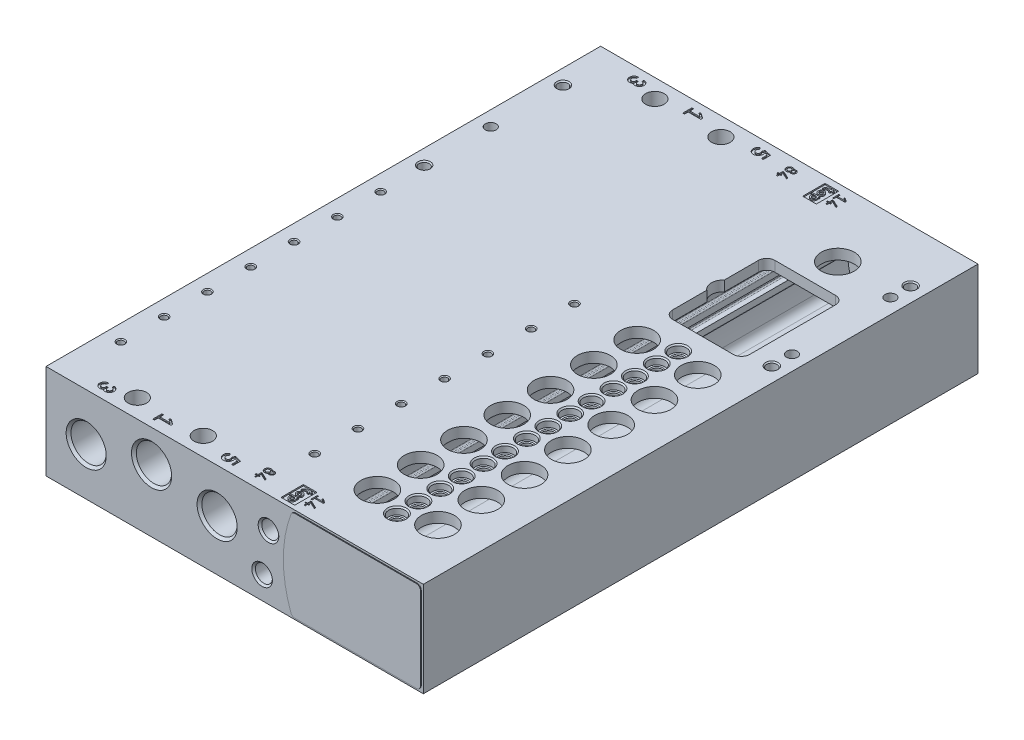
SolidWorks part; units mm, degrees
ref_plane "Ebene vorne" through (0, 0, 0) normal (0, 0, 1) x (1, 0, 0)
ref_plane "Ebene oben" through (0, 0, 0) normal (0, 1, 0) x (1, 0, 0)
ref_plane "Ebene rechts" through (0, 0, 0) normal (1, 0, 0) x (0, 0, -1)
sketch "Skizze1" plane through (0, 0, 0) normal (0, 0, 1) x (1, 0, 0)
  line L0 (0, -23) -> (91.5, -23)
  line L1 (91.5, -23) -> (91.5, 0)
  line L2 (91.5, 0) -> (0, 0)
  line L3 (0, 0) -> (0, -23)
  line L4 (59.6, -8.95) -> (59.6, -10.45)
  line L5 (59.9, -10.75) -> (61.1, -10.75)
  line L6 (61.1, -10.75) -> (61.1, -12.2)
  line L7 (60.8, -12.5) -> (60.0805, -12.5)
  line L8 (62.3938, -19.25) -> (83.8, -19.25)
  line L9 (85.8, -17.25) -> (85.8, -10.75)
  line L10 (85.8, -10.75) -> (87, -10.75)
  line L11 (87.3, -10.45) -> (87.3, -8.95)
  line L12 (87, -8.65) -> (85.8, -8.65)
  line L13 (85.8, -8.65) -> (85.8, -4.5)
  line L14 (83.8, -2.5) -> (62.71, -2.5)
  line L15 (60.4868, -6.9) -> (60.8, -6.9)
  line L16 (61.1, -7.2) -> (61.1, -8.65)
  line L17 (61.1, -8.65) -> (59.9, -8.65)
  arc A0 (59.6, -10.45) -> (59.9, -10.75) centre (59.9, -10.45) ccw
  arc A1 (61.1, -12.2) -> (60.8, -12.5) centre (60.8, -12.2) cw
  arc A2 (60.0805, -12.5) -> (59.7809, -12.8141) centre (60.0805, -12.8) ccw
  arc A3 (59.7809, -12.8141) -> (60.4433, -17.6923) centre (87.75, -11.5) ccw
  arc A4 (60.4433, -17.6923) -> (62.3938, -19.25) centre (62.3938, -17.25) ccw
  arc A5 (83.8, -19.25) -> (85.8, -17.25) centre (83.8, -17.25) ccw
  arc A6 (87, -10.75) -> (87.3, -10.45) centre (87, -10.45) ccw
  arc A7 (87.3, -8.95) -> (87, -8.65) centre (87, -8.95) ccw
  arc A8 (85.8, -4.5) -> (83.8, -2.5) centre (83.8, -4.5) ccw
  arc A9 (62.71, -2.5) -> (60.7839, -3.9615) centre (62.71, -4.5) ccw
  arc A10 (60.7839, -3.9615) -> (60.1916, -6.5469) centre (87.75, -11.5) ccw
  arc A11 (60.1916, -6.5469) -> (60.4868, -6.9) centre (60.4868, -6.6) ccw
  arc A12 (60.8, -6.9) -> (61.1, -7.2) centre (60.8, -7.2) cw
  arc A13 (59.9, -8.65) -> (59.6, -8.95) centre (59.9, -8.95) ccw
extrude "Aufsatz-Linear austragen1" add sketch "Skizze1" along normal blind 134.5
ref_plane "Ebene1" through (9.75, 0, 0) normal (1, 0, 0) x (0, 0, -1)
sketch "Skizze2" plane through (9.75, 0, 0) normal (1, 0, 0) x (0, 0, -1)
  line L0 (0, -11.5) -> (0, -16.364)
  line L1 (0, -16.364) -> (-0.581, -15.783)
  line L2 (-0.581, -15.783) -> (-9.5, -15.783)
  line L3 (-9.5, -15.783) -> (-9.5, -11.5)
  line L4 (-9.5, -11.5) -> (0, -11.5)
  line L5 (-9.5, -11.5) -> (0, -11.5) construction
revolve "Schnitt-Rotation1" cut sketch "Skizze2" angle 360 about L5 reverse direction yes
cosmetic thread "Gewindedarstellung1" parameters "D1"=7, "D2"=9.728
sketch "Skizze3" plane through (9.75, 0, 0) normal (1, 0, 0) x (0, 0, -1)
  line L0 (-125, -11.5) -> (-125, -15.783)
  line L1 (-125, -15.783) -> (-133.919, -15.783)
  line L2 (-133.919, -15.783) -> (-134.5, -16.364)
  line L3 (-134.5, -16.364) -> (-134.5, -11.5)
  line L4 (-134.5, -11.5) -> (-125, -11.5)
  line L5 (-134.5, -11.5) -> (-125, -11.5) construction
revolve "Schnitt-Rotation2" cut sketch "Skizze3" angle 360 about L5 reverse direction yes
cosmetic thread "Gewindedarstellung2" parameters "D1"=7, "D2"=9.728
ref_plane "Ebene2" through (25.6, 0, 0) normal (1, 0, 0) x (0, 0, -1)
sketch "Skizze4" plane through (25.6, 0, 0) normal (1, 0, 0) x (0, 0, -1)
  line L0 (0, -7.8) -> (0, -12.664)
  line L1 (0, -12.664) -> (-0.581, -12.083)
  line L2 (-0.581, -12.083) -> (-9.5, -12.083)
  line L3 (-9.5, -12.083) -> (-9.5, -7.8)
  line L4 (-9.5, -7.8) -> (0, -7.8)
  line L5 (-9.5, -7.8) -> (0, -7.8) construction
revolve "Schnitt-Rotation3" cut sketch "Skizze4" angle 360 about L5 reverse direction yes
cosmetic thread "Gewindedarstellung3" parameters "D1"=7, "D2"=9.728
sketch "Skizze5" plane through (25.6, 0, 0) normal (1, 0, 0) x (0, 0, -1)
  line L0 (-125, -7.8) -> (-125, -12.083)
  line L1 (-125, -12.083) -> (-133.919, -12.083)
  line L2 (-133.919, -12.083) -> (-134.5, -12.664)
  line L3 (-134.5, -12.664) -> (-134.5, -7.8)
  line L4 (-134.5, -7.8) -> (-125, -7.8)
  line L5 (-134.5, -7.8) -> (-125, -7.8) construction
revolve "Schnitt-Rotation4" cut sketch "Skizze5" angle 360 about L5 reverse direction yes
cosmetic thread "Gewindedarstellung4" parameters "D1"=7, "D2"=9.728
ref_plane "Ebene3" through (41.5, 0, 0) normal (1, 0, 0) x (0, 0, -1)
sketch "Skizze6" plane through (41.5, 0, 0) normal (1, 0, 0) x (0, 0, -1)
  line L0 (0, -10.6) -> (0, -15.464)
  line L1 (0, -15.464) -> (-0.581, -14.883)
  line L2 (-0.581, -14.883) -> (-9.5, -14.883)
  line L3 (-9.5, -14.883) -> (-9.5, -10.6)
  line L4 (-9.5, -10.6) -> (0, -10.6)
  line L5 (-9.5, -10.6) -> (0, -10.6) construction
revolve "Schnitt-Rotation5" cut sketch "Skizze6" angle 360 about L5 reverse direction yes
cosmetic thread "Gewindedarstellung5" parameters "D1"=7, "D2"=9.728
sketch "Skizze7" plane through (41.5, 0, 0) normal (1, 0, 0) x (0, 0, -1)
  line L0 (-125, -10.6) -> (-125, -14.883)
  line L1 (-125, -14.883) -> (-133.919, -14.883)
  line L2 (-133.919, -14.883) -> (-134.5, -15.464)
  line L3 (-134.5, -15.464) -> (-134.5, -10.6)
  line L4 (-134.5, -10.6) -> (-125, -10.6)
  line L5 (-134.5, -10.6) -> (-125, -10.6) construction
revolve "Schnitt-Rotation6" cut sketch "Skizze7" angle 360 about L5 reverse direction yes
cosmetic thread "Gewindedarstellung6" parameters "D1"=7, "D2"=9.728
ref_plane "Ebene4" through (52.4, 0, 0) normal (1, 0, 0) x (0, 0, -1)
sketch "Skizze8" plane through (52.4, 0, 0) normal (1, 0, 0) x (0, 0, -1)
  line L0 (0, -17.5) -> (0, -20)
  line L1 (0, -20) -> (-0.433, -19.567)
  line L2 (-0.433, -19.567) -> (-5, -19.567)
  line L3 (-5, -19.567) -> (-5, -17.5)
  line L4 (-5, -17.5) -> (0, -17.5)
  line L5 (-5, -17.5) -> (0, -17.5) construction
revolve "Schnitt-Rotation7" cut sketch "Skizze8" angle 360 about L5 reverse direction yes
cosmetic thread "Gewindedarstellung7" parameters "D1"=5, "D2"=5
sketch "Skizze9" plane through (52.4, 0, 0) normal (1, 0, 0) x (0, 0, -1)
  line L0 (-129.5, -17.5) -> (-129.5, -19.567)
  line L1 (-129.5, -19.567) -> (-134.067, -19.567)
  line L2 (-134.067, -19.567) -> (-134.5, -20)
  line L3 (-134.5, -20) -> (-134.5, -17.5)
  line L4 (-134.5, -17.5) -> (-129.5, -17.5)
  line L5 (-134.5, -17.5) -> (-129.5, -17.5) construction
revolve "Schnitt-Rotation8" cut sketch "Skizze9" angle 360 about L5 reverse direction yes
cosmetic thread "Gewindedarstellung8" parameters "D1"=5, "D2"=5
ref_plane "Ebene5" through (53.95, 0, 0) normal (1, 0, 0) x (0, 0, -1)
sketch "Skizze10" plane through (53.95, 0, 0) normal (1, 0, 0) x (0, 0, -1)
  line L0 (0, -7.5) -> (0, -10)
  line L1 (0, -10) -> (-0.433, -9.567)
  line L2 (-0.433, -9.567) -> (-5, -9.567)
  line L3 (-5, -9.567) -> (-5, -7.5)
  line L4 (-5, -7.5) -> (0, -7.5)
  line L5 (-5, -7.5) -> (0, -7.5) construction
revolve "Schnitt-Rotation9" cut sketch "Skizze10" angle 360 about L5 reverse direction yes
cosmetic thread "Gewindedarstellung9" parameters "D1"=5, "D2"=5
sketch "Skizze11" plane through (53.95, 0, 0) normal (1, 0, 0) x (0, 0, -1)
  line L0 (-129.5, -7.5) -> (-129.5, -9.567)
  line L1 (-129.5, -9.567) -> (-134.067, -9.567)
  line L2 (-134.067, -9.567) -> (-134.5, -10)
  line L3 (-134.5, -10) -> (-134.5, -7.5)
  line L4 (-134.5, -7.5) -> (-129.5, -7.5)
  line L5 (-134.5, -7.5) -> (-129.5, -7.5) construction
revolve "Schnitt-Rotation10" cut sketch "Skizze11" angle 360 about L5 reverse direction yes
cosmetic thread "Gewindedarstellung10" parameters "D1"=5, "D2"=5
hole_wizard "Bohrung1" positions "Skizze13" profile "Skizze12" legacy
sketch "Skizze13" plane through (0, 0, 0) normal (0, 1, 0) x (1, 0, 0)
  point P0 (17.65, -4.5)
sketch "Skizze12" plane through (17.65, 0, 4.5) normal (1, 0, 0) x (0, 0, 1)
  line L0 (0, 0) -> (0, 23)
  line L1 (0, 23) -> (2.25, 23)
  line L2 (2.25, 23) -> (2.25, 0)
  line L3 (2.25, 0) -> (0, 0)
  line L4 (0, 110) -> (0, -10) construction
  dimension "Durchmesser" = 4.5
  dimension "Tiefe" = 23
sketch "Skizze14" plane through (0, 0, 0) normal (0, 1, 0) x (1, 0, 0)
  line L0 (17.65, -4.5) -> (33.65, -4.5)
  line L1 (17.65, -4.5) -> (17.65, -130)
pattern_linear "Lineares Muster1" count 2 spacing 16 along (1, 0, 0) count 2 spacing 125.5 along (0, 0, 1) of "Bohrung1"
hole_wizard "Bohrung2" positions "Skizze16" profile "Skizze15" legacy
sketch "Skizze16" plane through (0, 0, 0) normal (0, 1, 0) x (1, 0, 0)
  point P0 (80.8, -57.25)
sketch "Skizze15" plane through (80.8, 0, 57.25) normal (1, 0, 0) x (0, 0, 1)
  line L0 (0, 0) -> (0, 5)
  line L1 (0, 5) -> (4, 5)
  line L2 (4, 5) -> (4, 0)
  line L3 (4, 0) -> (0, 0)
  line L4 (0, 110) -> (0, -10) construction
  dimension "Durchmesser" = 8
  dimension "Tiefe" = 5
sketch "Skizze17" plane through (0, 0, 0) normal (0, 1, 0) x (1, 0, 0)
  line L0 (80.8, -57.25) -> (80.8, -120.25)
pattern_linear "Lineares Muster2" count 7 spacing 10.5 along (0, 0, 1) of "Bohrung2"
hole_wizard "Bohrung3" positions "Skizze19" profile "Skizze18" legacy
sketch "Skizze19" plane through (0, 0, 0) normal (0, 1, 0) x (1, 0, 0)
  point P0 (66.1, -57.25)
sketch "Skizze18" plane through (66.1, 0, 57.25) normal (1, 0, 0) x (0, 0, 1)
  line L0 (0, 0) -> (0, 5)
  line L1 (0, 5) -> (4, 5)
  line L2 (4, 5) -> (4, 0)
  line L3 (4, 0) -> (0, 0)
  line L4 (0, 110) -> (0, -10) construction
  dimension "Durchmesser" = 8
  dimension "Tiefe" = 5
sketch "Skizze20" plane through (0, 0, 0) normal (0, 1, 0) x (1, 0, 0)
  line L0 (66.1, -57.25) -> (66.1, -120.25)
pattern_linear "Lineares Muster3" count 7 spacing 10.5 along (0, 0, 1) of "Bohrung3"
ref_plane "Ebene6" through (73.45, 0, 0) normal (1, 0, 0) x (0, 0, -1)
sketch "Skizze21" plane through (73.45, 0, 0) normal (1, 0, 0) x (0, 0, -1)
  line L0 (-54.65, -3) -> (-56, -3)
  line L1 (-56, -3) -> (-56, -1.9)
  line L2 (-56, -1.9) -> (-56.2, -1.7)
  line L3 (-56.2, -1.7) -> (-56.65, -1.7)
  line L4 (-56.65, -1.7) -> (-56.65, -0.3)
  line L5 (-56.65, -0.3) -> (-56.95, 0)
  line L6 (-56.95, 0) -> (-54.65, 0)
  line L7 (-54.65, 0) -> (-54.65, -3)
  line L8 (-54.65, 0) -> (-54.65, -3) construction
revolve "Schnitt-Rotation11" cut sketch "Skizze21" angle 360 about L8 reverse direction yes
sketch "Skizze22" plane through (0, 0, 0) normal (0, 1, 0) x (1, 0, 0)
  line L0 (73.45, -54.65) -> (73.45, -117.65)
pattern_linear "Lineares Muster4" count 7 spacing 10.5 along (0, 0, 1) of "Schnitt-Rotation11"
sketch "Skizze23" plane through (73.45, 0, 0) normal (1, 0, 0) x (0, 0, -1)
  line L0 (-59.85, -3) -> (-61.2, -3)
  line L1 (-61.2, -3) -> (-61.2, -1.9)
  line L2 (-61.2, -1.9) -> (-61.4, -1.7)
  line L3 (-61.4, -1.7) -> (-61.85, -1.7)
  line L4 (-61.85, -1.7) -> (-61.85, -0.3)
  line L5 (-61.85, -0.3) -> (-62.15, 0)
  line L6 (-62.15, 0) -> (-59.85, 0)
  line L7 (-59.85, 0) -> (-59.85, -3)
  line L8 (-59.85, 0) -> (-59.85, -3) construction
revolve "Schnitt-Rotation12" cut sketch "Skizze23" angle 360 about L8 reverse direction yes
sketch "Skizze24" plane through (0, 0, 0) normal (0, 1, 0) x (1, 0, 0)
  line L0 (73.45, -59.85) -> (73.45, -122.85)
pattern_linear "Lineares Muster5" count 7 spacing 10.5 along (0, 0, 1) of "Schnitt-Rotation12"
ref_plane "Ebene7" through (50.9, 0, 0) normal (1, 0, 0) x (0, 0, -1)
hole_wizard "Bohrung4" positions "Skizze26" profile "Skizze25" legacy
sketch "Skizze26" plane through (0, 0, 0) normal (0, 1, 0) x (1, 0, 0)
  point P0 (50.9, -57.25)
sketch "Skizze25" plane through (50.9, 0, 57.25) normal (1, 0, 0) x (0, 0, 1)
  line L0 (0, 0) -> (0, 5.7524)
  line L1 (0, 5.7524) -> (0.7835, 5.3)
  line L2 (0.7835, 5.3) -> (0.7835, 0.2165)
  line L3 (0.7835, 0.2165) -> (1, 0)
  line L4 (1, 0) -> (0, 0)
  line L5 (0, -14.3089) -> (0, 102.4216) construction
  line L6 (0, 5.7524) -> (-0.7835, 5.3) construction
  line L7 (-0.7835, 0.2165) -> (-1, 0) construction
  dimension "Durchmesser" = 1.567
  dimension "Tiefe" = 5.3
  dimension "Senkdurchmesser1" = 2
  dimension "Senkwinkel1" = 90
  dimension "Spitzenwinkel" = 120
cosmetic thread "Gewindedarstellung11" parameters "D1"=4, "D2"=2
sketch "Skizze27" plane through (0, 0, 0) normal (0, 1, 0) x (1, 0, 0)
  line L0 (50.9, -57.25) -> (50.9, -120.25)
pattern_linear "Lineares Muster6" count 7 spacing 10.5 along (0, 0, 1) of "Bohrung4"
ref_plane "Ebene8" through (3.9, 0, 0) normal (1, 0, 0) x (0, 0, -1)
hole_wizard "Bohrung5" positions "Skizze29" profile "Skizze28" legacy
sketch "Skizze29" plane through (0, 0, 0) normal (0, 1, 0) x (1, 0, 0)
  point P0 (3.9, -57.25)
sketch "Skizze28" plane through (3.9, 0, 57.25) normal (1, 0, 0) x (0, 0, 1)
  line L0 (0, 0) -> (0, 5.7524)
  line L1 (0, 5.7524) -> (0.7835, 5.3)
  line L2 (0.7835, 5.3) -> (0.7835, 0.2165)
  line L3 (0.7835, 0.2165) -> (1, 0)
  line L4 (1, 0) -> (0, 0)
  line L5 (0, -14.3089) -> (0, 102.4216) construction
  line L6 (0, 5.7524) -> (-0.7835, 5.3) construction
  line L7 (-0.7835, 0.2165) -> (-1, 0) construction
  dimension "Durchmesser" = 1.567
  dimension "Tiefe" = 5.3
  dimension "Senkdurchmesser1" = 2
  dimension "Senkwinkel1" = 90
  dimension "Spitzenwinkel" = 120
cosmetic thread "Gewindedarstellung12" parameters "D1"=4, "D2"=2
sketch "Skizze30" plane through (0, 0, 0) normal (0, 1, 0) x (1, 0, 0)
  line L0 (3.9, -57.25) -> (3.9, -120.25)
pattern_linear "Lineares Muster7" count 7 spacing 10.5 along (0, 0, 1) of "Bohrung5"
hole_wizard "Bohrung6" positions "Skizze32" profile "Skizze31" legacy
sketch "Skizze32" plane through (0, 0, 0) normal (0, 1, 0) x (1, 0, 0)
  point P0 (74, -16.5)
sketch "Skizze31" plane through (74, 0, 16.5) normal (1, 0, 0) x (0, 0, 1)
  line L0 (0, 0) -> (0, 2.5)
  line L1 (0, 2.5) -> (4, 2.5)
  line L2 (4, 2.5) -> (4, 0)
  line L3 (4, 0) -> (0, 0)
  line L4 (0, 110) -> (0, -10) construction
  dimension "Durchmesser" = 8
  dimension "Tiefe" = 2.5
ref_plane "Ebene9" through (3.6, 0, 0) normal (1, 0, 0) x (0, 0, -1)
hole_wizard "Bohrung7" positions "Skizze34" profile "Skizze33" legacy
sketch "Skizze34" plane through (0, 0, 0) normal (0, 1, 0) x (1, 0, 0)
  point P0 (3.6, -12.75)
sketch "Skizze33" plane through (3.6, 0, 12.75) normal (1, 0, 0) x (0, 0, 1)
  line L0 (0, 0) -> (0, 7.7099)
  line L1 (0, 7.7099) -> (1.2295, 7)
  line L2 (1.2295, 7) -> (1.2295, 0.2705)
  line L3 (1.2295, 0.2705) -> (1.5, 0)
  line L4 (1.5, 0) -> (0, 0)
  line L5 (0, -14.3089) -> (0, 102.4216) construction
  line L6 (0, 7.7099) -> (-1.2295, 7) construction
  line L7 (-1.2295, 0.2705) -> (-1.5, 0) construction
  dimension "Durchmesser" = 2.459
  dimension "Tiefe" = 7
  dimension "Senkdurchmesser1" = 3
  dimension "Senkwinkel1" = 90
  dimension "Spitzenwinkel" = 120
cosmetic thread "Gewindedarstellung13" parameters "D1"=5.5, "D2"=3
sketch "Skizze35" plane through (0, 0, 0) normal (0, 1, 0) x (1, 0, 0)
  line L0 (3.6, -12.75) -> (87.9, -12.75)
  line L1 (3.6, -12.75) -> (3.6, -46.4)
pattern_linear "Lineares Muster8" count 2 spacing 84.3 along (1, 0, 0) count 2 spacing 33.65 along (0, 0, 1) of "Bohrung7"
ref_plane "Ebene10" through (0, -2, 0) normal (0, 1, 0) x (1, 0, 0)
ref_plane "Ebene11" through (0, -9, 0) normal (0, 1, 0) x (1, 0, 0)
sketch "Skizze36" plane through (0, -9, 0) normal (0, 1, 0) x (1, 0, 0)
  circle A0 centre (3.6, -30.25) radius 1.3
extrude "Schnitt-Linear austragen1" cut sketch "Skizze36" along normal blind 11
sketch "Skizze37" plane through (0, -2, 0) normal (0, 1, 0) x (1, 0, 0)
  line L0 (3.6, -30.25) -> (87.9, -17.65)
  line L1 (3.6, -30.25) -> (87.9, -41.5)
pattern_linear "Lineares Muster9" count 2 spacing 85.2364 along (0.989, 0, -0.1478) count 2 spacing 85.0474 along (0.9912, 0, 0.1323) skipping (1, 1) of "Schnitt-Linear austragen1"
sketch "Skizze38" plane through (0, 0, 0) normal (0, 1, 0) x (1, 0, 0)
  line L0 (64.1, -38.3713) -> (64.1, -46.65)
  line L1 (66.1, -48.65) -> (80.8, -48.65)
  line L2 (82.8, -46.65) -> (82.8, -25.85)
  line L3 (80.8, -23.85) -> (66.1, -23.85)
  line L4 (64.1, -25.85) -> (64.1, -34.1287)
  arc A0 (64.1, -34.1287) -> (64.1, -38.3713) centre (65.85, -36.25) ccw
  arc A1 (64.1, -46.65) -> (66.1, -48.65) centre (66.1, -46.65) ccw
  arc A2 (80.8, -48.65) -> (82.8, -46.65) centre (80.8, -46.65) ccw
  arc A3 (82.8, -25.85) -> (80.8, -23.85) centre (80.8, -25.85) ccw
  arc A4 (66.1, -23.85) -> (64.1, -25.85) centre (66.1, -25.85) ccw
extrude "Schnitt-Linear austragen2" cut sketch "Skizze38" against normal blind 5
ref_plane "Ebene12" through (0, 0, 20) normal (0, 0, 1) x (1, 0, 0)
sketch "Skizze39" plane through (0, 0, 20) normal (0, 0, 1) x (1, 0, 0)
  line L0 (0, -4.75) -> (0, -2.25)
  line L1 (0, -2.25) -> (0.433, -2.683)
  line L2 (0.433, -2.683) -> (41, -2.683)
  line L3 (41, -2.683) -> (41.4625, -2.95)
  line L4 (41.4625, -2.95) -> (46, -2.95)
  line L5 (46, -2.95) -> (46, -3.1)
  line L6 (46, -3.1) -> (55.75, -3.1)
  line L7 (55.75, -3.1) -> (56.7026, -4.75)
  line L8 (56.7026, -4.75) -> (0, -4.75)
  line L9 (56.7026, -4.75) -> (0, -4.75) construction
revolve "Schnitt-Rotation13" cut sketch "Skizze39" angle 360 about L9 reverse direction yes
cosmetic thread "Gewindedarstellung14" parameters "D1"=6, "D2"=5
ref_plane "Ebene13" through (0, 0, 36) normal (0, 0, 1) x (1, 0, 0)
sketch "Skizze40" plane through (0, 0, 36) normal (0, 0, 1) x (1, 0, 0)
  line L0 (0, -4.75) -> (0, -2.25)
  line L1 (0, -2.25) -> (0.433, -2.683)
  line L2 (0.433, -2.683) -> (13, -2.683)
  line L3 (13, -2.683) -> (14.1934, -4.75)
  line L4 (14.1934, -4.75) -> (0, -4.75)
  line L5 (14.1934, -4.75) -> (0, -4.75) construction
revolve "Schnitt-Rotation14" cut sketch "Skizze40" angle 360 about L5 reverse direction yes
cosmetic thread "Gewindedarstellung15" parameters "D1"=10, "D2"=5
ref_plane "Ebene14" through (0, -23, 0) normal (0, 1, 0) x (1, 0, 0)
ref_plane "Ebene15" through (0, 0, 57.25) normal (0, 0, 1) x (1, 0, 0)
sketch "Skizze41" plane through (0, 0, 57.25) normal (0, 0, 1) x (1, 0, 0)
  line L0 (0, -17.6) -> (0, -15.1)
  line L1 (0, -15.1) -> (0.433, -15.533)
  line L2 (0.433, -15.533) -> (6, -15.533)
  line L3 (6, -15.533) -> (6, -17.6)
  line L4 (6, -17.6) -> (0, -17.6)
  line L5 (6, -17.6) -> (0, -17.6) construction
revolve "Schnitt-Rotation15" cut sketch "Skizze41" angle 360 about L5 reverse direction yes
cosmetic thread "Gewindedarstellung16" parameters "D1"=6, "D2"=5
sketch "Skizze42" plane through (0, 0, 0) normal (1, 0, 0) x (0, 0, -1)
  line L0 (-57.25, -17.6) -> (-120.25, -17.6)
pattern_linear "Lineares Muster10" count 7 spacing 10.5 along (0, 0, 1) of "Schnitt-Rotation15"
ref_plane "Ebene16" through (0, 0, 53.15) normal (0, 0, 1) x (1, 0, 0)
sketch "Skizze43" plane through (0, 0, 53.15) normal (0, 0, 1) x (1, 0, 0)
  line L0 (0, -5.4) -> (0, -2.9)
  line L1 (0, -2.9) -> (0.433, -3.333)
  line L2 (0.433, -3.333) -> (6, -3.333)
  line L3 (6, -3.333) -> (6, -5.4)
  line L4 (6, -5.4) -> (0, -5.4)
  line L5 (6, -5.4) -> (0, -5.4) construction
revolve "Schnitt-Rotation16" cut sketch "Skizze43" angle 360 about L5 reverse direction yes
cosmetic thread "Gewindedarstellung17" parameters "D1"=6, "D2"=5
sketch "Skizze44" plane through (0, 0, 0) normal (1, 0, 0) x (0, 0, -1)
  line L0 (-53.15, -5.4) -> (-116.15, -5.4)
pattern_linear "Lineares Muster11" count 7 spacing 10.5 along (0, 0, 1) of "Schnitt-Rotation16"
ref_plane "Ebene17" through (0, 0, 42.25) normal (0, 0, 1) x (1, 0, 0)
ref_plane "Ebene18" through (0, 0, 32.25) normal (0, 0, 1) x (1, 0, 0)
ref_plane "Ebene19" through (0, 0, 29.25) normal (0, 0, 1) x (1, 0, 0)
ref_plane "Ebene20" through (0, 0, 19.75) normal (0, 0, 1) x (1, 0, 0)
ref_plane "Ebene21" through (0, 0, 13) normal (0, 0, 1) x (1, 0, 0)
ref_plane "Ebene22" through (0, 0, 126.5) normal (0, 0, 1) x (1, 0, 0)
ref_plane "Ebene23" through (0, 0, 0) normal (-1, 0, 0) x (0, 0, 1)
ref_plane "Ebene24" through (0, 0, 0) normal (-1, 0, 0) x (0, 0, 1)
ref_plane "Ebene25" through (0, 0, 0) normal (0, 0, 1) x (1, 0, 0)
sketch "Skizze45" plane through (0, 0, 0) normal (0, 0, 1) x (1, 0, 0)
  line L0 (60.5287, -22.5) -> (90, -22.5)
  line L1 (91, -21.5) -> (91, -1.5)
  line L2 (90, -0.5) -> (60.5287, -0.5)
  arc A0 (59.59, -1.1552) -> (59.59, -21.8448) centre (87.75, -11.5) ccw
  arc A1 (59.59, -21.8448) -> (60.5287, -22.5) centre (60.5287, -21.5) ccw
  arc A2 (90, -22.5) -> (91, -21.5) centre (90, -21.5) ccw
  arc A3 (91, -1.5) -> (90, -0.5) centre (90, -1.5) ccw
  arc A4 (60.5287, -0.5) -> (59.59, -1.1552) centre (60.5287, -1.5) ccw
extrude "Aufsatz-Linear austragen2" add sketch "Skizze45" against normal blind 0.2
ref_plane "Ebene26" through (0, 0, 134.5) normal (0, 0, 1) x (1, 0, 0)
sketch "Skizze46" plane through (0, 0, 134.5) normal (0, 0, 1) x (1, 0, 0)
  line L0 (60.5287, -22.5) -> (90, -22.5)
  line L1 (91, -21.5) -> (91, -1.5)
  line L2 (90, -0.5) -> (60.5287, -0.5)
  arc A0 (59.59, -1.1552) -> (59.59, -21.8448) centre (87.75, -11.5) ccw
  arc A1 (59.59, -21.8448) -> (60.5287, -22.5) centre (60.5287, -21.5) ccw
  arc A2 (90, -22.5) -> (91, -21.5) centre (90, -21.5) ccw
  arc A3 (91, -1.5) -> (90, -0.5) centre (90, -1.5) ccw
  arc A4 (60.5287, -0.5) -> (59.59, -1.1552) centre (60.5287, -1.5) ccw
extrude "Aufsatz-Linear austragen3" add sketch "Skizze46" along normal blind 0.2
ref_plane "Ebene27" through (0, -23, 0) normal (0, 1, 0) x (1, 0, 0)
ref_plane "Ebene28" through (0, 0, 0) normal (0, 1, 0) x (1, 0, 0)
sketch "Skizze47" plane through (0, 0, 0) normal (0, 1, 0) x (1, 0, 0)
  line L0 (60, -3.75) -> (60.3, -3.75)
  line L1 (60.3, -3.75) -> (60.3, -3.15)
  line L2 (60.3, -3.15) -> (62.4, -3.15)
  line L3 (62.4, -3.15) -> (62.4, -2.85)
  line L4 (62.4, -2.85) -> (61.4761, -2.203)
  line L5 (61.4761, -2.203) -> (61.3351, -2.4044)
  line L6 (61.3351, -2.4044) -> (61.9716, -2.85)
  line L7 (61.9716, -2.85) -> (60.3, -2.85)
  line L8 (60.3, -2.85) -> (60.3, -2.25)
  line L9 (60.3, -2.25) -> (60, -2.25)
  line L10 (60, -2.25) -> (60, -3.75)
extrude "Schnitt-Linear austragen3" cut sketch "Skizze47" along normal blind 0.3 and the other way blind 0.3
sketch "Skizze48" plane through (0, 0, 0) normal (0, 1, 0) x (1, 0, 0)
  line L0 (60, -5.3) -> (60.4, -5.3)
  line L1 (60.4, -5.3) -> (60.4, -5.83)
  line L2 (60.4, -5.83) -> (60.7, -5.83)
  line L3 (60.7, -5.83) -> (60.7, -5.3)
  line L4 (60.7, -5.3) -> (61, -5.3)
  line L5 (61, -5.3) -> (61, -5)
  line L6 (61, -5) -> (60.7, -5)
  line L7 (60.7, -5) -> (60.7, -4.5399)
  line L8 (60.7, -4.5399) -> (62.4, -5.3326)
  line L9 (62.4, -5.3326) -> (62.4, -5.0016)
  line L10 (62.4, -5.0016) -> (60.6166, -4.17)
  line L11 (60.6166, -4.17) -> (60.4, -4.17)
  line L12 (60.4, -4.17) -> (60.4, -5)
  line L13 (60.4, -5) -> (60, -5)
  line L14 (60, -5) -> (60, -5.3)
extrude "Schnitt-Linear austragen4" cut sketch "Skizze48" along normal blind 0.3 and the other way blind 0.3
sketch "Skizze49" plane through (0, 0, 0) normal (0, 1, 0) x (1, 0, 0)
  line L0 (56, -7) -> (59.3, -7)
  line L1 (59.3, -7) -> (59.3, -1.6)
  line L2 (59.3, -1.6) -> (56, -1.6)
  line L3 (56, -1.6) -> (56, -7)
  line L4 (56.75, -2.95) -> (57.05, -2.95)
  line L5 (57.5, -2.5) -> (58.1, -2.5)
  line L6 (58.1, -2.5) -> (58.1, -2.8)
  line L7 (58.1, -2.8) -> (58.4, -2.8)
  line L8 (58.4, -2.8) -> (58.4, -2.5)
  line L9 (58.4, -2.5) -> (58.85, -2.5)
  line L10 (58.85, -2.5) -> (58.85, -2.2)
  line L11 (58.85, -2.2) -> (58.4, -2.2)
  line L12 (58.4, -2.2) -> (58.4, -1.9)
  line L13 (58.4, -1.9) -> (58.1, -1.9)
  line L14 (58.1, -1.9) -> (58.1, -2.2)
  line L15 (58.1, -2.2) -> (57.5, -2.2)
  line L16 (58.138, -4.3943) -> (57.878, -4.2442)
  line L17 (57.9005, -4.2052) -> (58.1605, -4.3553)
  line L18 (56.375, -5.35) -> (57.5, -5.35)
  line L19 (57.3384, -5.38) -> (56.8786, -5.38)
  line L20 (58.1, -5.35) -> (58.25, -5.35)
  line L21 (58.25, -5.35) -> (58.25, -5.05)
  line L22 (58.25, -5.05) -> (56.375, -5.05)
  line L23 (56.375, -5.05) -> (56.375, -5.35)
  arc A0 (57.05, -2.95) -> (57.5, -2.5) centre (57.5, -2.95) cw
  arc A1 (57.5, -2.2) -> (56.75, -2.95) centre (57.5, -2.95) ccw
  arc A2 (58.1605, -4.3553) -> (58.138, -4.3943) centre (57.5, -4) ccw
  arc A3 (57.878, -4.2442) -> (57.9005, -4.2052) centre (57.5, -4) cw
  arc A4 (57.5, -5.35) -> (57.3384, -5.38) centre (57.5, -5.8) cw
  arc A5 (56.8786, -5.38) -> (58.1, -5.35) centre (57.5, -5.8) ccw
extrude "Schnitt-Linear austragen5" cut sketch "Skizze49" along normal blind 0.3 and the other way blind 0.3
sketch "Skizze50" plane through (0, 0, 0) normal (0, 1, 0) x (1, 0, 0)
  arc A0 (49.3895, -2.4591) -> (49.3895, -3.5409) centre (48.8, -3) ccw
  arc A1 (49.3895, -3.5409) -> (49.3895, -2.4591) centre (49.75, -3) ccw
  circle A2 centre (49.75, -3) radius 0.35
  circle A3 centre (48.8, -3) radius 0.45
extrude "Schnitt-Linear austragen6" cut sketch "Skizze50" along normal blind 0.3 and the other way blind 0.3
sketch "Skizze51" plane through (0, 0, 0) normal (0, 1, 0) x (1, 0, 0)
  line L0 (48, -5.3) -> (48.4, -5.3)
  line L1 (48.4, -5.3) -> (48.4, -5.83)
  line L2 (48.4, -5.83) -> (48.7, -5.83)
  line L3 (48.7, -5.83) -> (48.7, -5.3)
  line L4 (48.7, -5.3) -> (49, -5.3)
  line L5 (49, -5.3) -> (49, -5)
  line L6 (49, -5) -> (48.7, -5)
  line L7 (48.7, -5) -> (48.7, -4.5399)
  line L8 (48.7, -4.5399) -> (50.4, -5.3326)
  line L9 (50.4, -5.3326) -> (50.4, -5.0016)
  line L10 (50.4, -5.0016) -> (48.6166, -4.17)
  line L11 (48.6166, -4.17) -> (48.4, -4.17)
  line L12 (48.4, -4.17) -> (48.4, -5)
  line L13 (48.4, -5) -> (48, -5)
  line L14 (48, -5) -> (48, -5.3)
extrude "Schnitt-Linear austragen7" cut sketch "Skizze51" along normal blind 0.3 and the other way blind 0.3
sketch "Skizze52" plane through (0, 0, 0) normal (0, 1, 0) x (1, 0, 0)
  line L0 (42.2971, -2.4929) -> (43.066, -2.685)
  line L1 (43.066, -2.685) -> (43.066, -4.095)
  line L2 (43.066, -4.095) -> (43.504, -4.095)
  line L3 (43.504, -4.095) -> (43.504, -2.343)
  line L4 (43.504, -2.343) -> (41.8464, -1.9289)
  line L5 (41.8464, -1.9289) -> (41.6425, -2.489)
  line L6 (41.6425, -2.489) -> (41.6425, -2.6137)
  line L7 (40.9855, -2.4586) -> (40.6251, -1.944)
  arc A0 (40.6251, -1.944) -> (42.2971, -2.4929) centre (41.2045, -3) ccw
  arc A1 (41.6425, -2.6137) -> (40.9855, -2.4586) centre (41.2045, -3) cw
extrude "Schnitt-Linear austragen8" cut sketch "Skizze52" along normal blind 0.3 and the other way blind 0.3
sketch "Skizze53" plane through (0, 0, 0) normal (0, 1, 0) x (1, 0, 0)
  line L0 (24, -4.095) -> (24.438, -4.095)
  line L1 (24.438, -4.095) -> (24.438, -3.219)
  line L2 (24.438, -3.219) -> (27.504, -3.219)
  line L3 (27.504, -3.219) -> (27.504, -2.781)
  line L4 (27.504, -2.781) -> (26.155, -1.8364)
  line L5 (26.155, -1.8364) -> (25.9492, -2.1304)
  line L6 (25.9492, -2.1304) -> (26.8785, -2.781)
  line L7 (26.8785, -2.781) -> (24.438, -2.781)
  line L8 (24.438, -2.781) -> (24.438, -1.905)
  line L9 (24.438, -1.905) -> (24, -1.905)
  line L10 (24, -1.905) -> (24, -4.095)
extrude "Schnitt-Linear austragen9" cut sketch "Skizze53" along normal blind 0.3 and the other way blind 0.3
sketch "Skizze54" plane through (0, 0, 0) normal (0, 1, 0) x (1, 0, 0)
  line L0 (12.409, -1.905) -> (12.409, -2.416)
  line L1 (11.971, -3.146) -> (11.971, -2.854)
  line L2 (11.971, -2.854) -> (11.533, -2.854)
  line L3 (11.533, -2.854) -> (11.533, -3.146)
  line L4 (11.095, -2.416) -> (11.095, -1.905)
  arc A0 (11.095, -1.905) -> (11.752, -3.876) centre (11.095, -3) ccw
  arc A1 (11.752, -3.876) -> (12.409, -1.905) centre (12.409, -3) ccw
  arc A2 (12.409, -2.416) -> (12.409, -3.584) centre (12.409, -3) cw
  arc A3 (12.409, -3.584) -> (11.971, -3.146) centre (12.409, -3.146) cw
  arc A4 (11.533, -3.146) -> (11.095, -3.584) centre (11.095, -3.146) cw
  arc A5 (11.095, -3.584) -> (11.095, -2.416) centre (11.095, -3) cw
extrude "Schnitt-Linear austragen10" cut sketch "Skizze54" along normal blind 0.3 and the other way blind 0.3
sketch "Skizze55" plane through (0, 0, 0) normal (0, 1, 0) x (1, 0, 0)
  line L0 (60, -130.25) -> (60.3, -130.25)
  line L1 (60.3, -130.25) -> (60.3, -129.65)
  line L2 (60.3, -129.65) -> (62.4, -129.65)
  line L3 (62.4, -129.65) -> (62.4, -129.35)
  line L4 (62.4, -129.35) -> (61.4761, -128.703)
  line L5 (61.4761, -128.703) -> (61.3351, -128.9044)
  line L6 (61.3351, -128.9044) -> (61.9716, -129.35)
  line L7 (61.9716, -129.35) -> (60.3, -129.35)
  line L8 (60.3, -129.35) -> (60.3, -128.75)
  line L9 (60.3, -128.75) -> (60, -128.75)
  line L10 (60, -128.75) -> (60, -130.25)
extrude "Schnitt-Linear austragen11" cut sketch "Skizze55" along normal blind 0.3 and the other way blind 0.3
sketch "Skizze56" plane through (0, 0, 0) normal (0, 1, 0) x (1, 0, 0)
  line L0 (60, -131.8) -> (60.4, -131.8)
  line L1 (60.4, -131.8) -> (60.4, -132.33)
  line L2 (60.4, -132.33) -> (60.7, -132.33)
  line L3 (60.7, -132.33) -> (60.7, -131.8)
  line L4 (60.7, -131.8) -> (61, -131.8)
  line L5 (61, -131.8) -> (61, -131.5)
  line L6 (61, -131.5) -> (60.7, -131.5)
  line L7 (60.7, -131.5) -> (60.7, -131.0399)
  line L8 (60.7, -131.0399) -> (62.4, -131.8326)
  line L9 (62.4, -131.8326) -> (62.4, -131.5016)
  line L10 (62.4, -131.5016) -> (60.6166, -130.67)
  line L11 (60.6166, -130.67) -> (60.4, -130.67)
  line L12 (60.4, -130.67) -> (60.4, -131.5)
  line L13 (60.4, -131.5) -> (60, -131.5)
  line L14 (60, -131.5) -> (60, -131.8)
extrude "Schnitt-Linear austragen12" cut sketch "Skizze56" along normal blind 0.3 and the other way blind 0.3
sketch "Skizze57" plane through (0, 0, 0) normal (0, 1, 0) x (1, 0, 0)
  line L0 (56, -133.5) -> (59.3, -133.5)
  line L1 (59.3, -133.5) -> (59.3, -128.1)
  line L2 (59.3, -128.1) -> (56, -128.1)
  line L3 (56, -128.1) -> (56, -133.5)
  line L4 (56.75, -129.45) -> (57.05, -129.45)
  line L5 (57.5, -129) -> (58.1, -129)
  line L6 (58.1, -129) -> (58.1, -129.3)
  line L7 (58.1, -129.3) -> (58.4, -129.3)
  line L8 (58.4, -129.3) -> (58.4, -129)
  line L9 (58.4, -129) -> (58.85, -129)
  line L10 (58.85, -129) -> (58.85, -128.7)
  line L11 (58.85, -128.7) -> (58.4, -128.7)
  line L12 (58.4, -128.7) -> (58.4, -128.4)
  line L13 (58.4, -128.4) -> (58.1, -128.4)
  line L14 (58.1, -128.4) -> (58.1, -128.7)
  line L15 (58.1, -128.7) -> (57.5, -128.7)
  line L16 (58.138, -130.8943) -> (57.878, -130.7442)
  line L17 (57.9005, -130.7052) -> (58.1605, -130.8553)
  line L18 (56.375, -131.85) -> (57.5, -131.85)
  line L19 (57.3384, -131.88) -> (56.8786, -131.88)
  line L20 (58.1, -131.85) -> (58.25, -131.85)
  line L21 (58.25, -131.85) -> (58.25, -131.55)
  line L22 (58.25, -131.55) -> (56.375, -131.55)
  line L23 (56.375, -131.55) -> (56.375, -131.85)
  arc A0 (57.05, -129.45) -> (57.5, -129) centre (57.5, -129.45) cw
  arc A1 (57.5, -128.7) -> (56.75, -129.45) centre (57.5, -129.45) ccw
  arc A2 (58.1605, -130.8553) -> (58.138, -130.8943) centre (57.5, -130.5) ccw
  arc A3 (57.878, -130.7442) -> (57.9005, -130.7052) centre (57.5, -130.5) cw
  arc A4 (57.5, -131.85) -> (57.3384, -131.88) centre (57.5, -132.3) cw
  arc A5 (56.8786, -131.88) -> (58.1, -131.85) centre (57.5, -132.3) ccw
extrude "Schnitt-Linear austragen13" cut sketch "Skizze57" along normal blind 0.3 and the other way blind 0.3
sketch "Skizze58" plane through (0, 0, 0) normal (0, 1, 0) x (1, 0, 0)
  arc A0 (49.3895, -128.9591) -> (49.3895, -130.0409) centre (48.8, -129.5) ccw
  arc A1 (49.3895, -130.0409) -> (49.3895, -128.9591) centre (49.75, -129.5) ccw
  circle A2 centre (49.75, -129.5) radius 0.35
  circle A3 centre (48.8, -129.5) radius 0.45
extrude "Schnitt-Linear austragen14" cut sketch "Skizze58" along normal blind 0.3 and the other way blind 0.3
sketch "Skizze59" plane through (0, 0, 0) normal (0, 1, 0) x (1, 0, 0)
  line L0 (48, -131.8) -> (48.4, -131.8)
  line L1 (48.4, -131.8) -> (48.4, -132.33)
  line L2 (48.4, -132.33) -> (48.7, -132.33)
  line L3 (48.7, -132.33) -> (48.7, -131.8)
  line L4 (48.7, -131.8) -> (49, -131.8)
  line L5 (49, -131.8) -> (49, -131.5)
  line L6 (49, -131.5) -> (48.7, -131.5)
  line L7 (48.7, -131.5) -> (48.7, -131.0399)
  line L8 (48.7, -131.0399) -> (50.4, -131.8326)
  line L9 (50.4, -131.8326) -> (50.4, -131.5016)
  line L10 (50.4, -131.5016) -> (48.6166, -130.67)
  line L11 (48.6166, -130.67) -> (48.4, -130.67)
  line L12 (48.4, -130.67) -> (48.4, -131.5)
  line L13 (48.4, -131.5) -> (48, -131.5)
  line L14 (48, -131.5) -> (48, -131.8)
extrude "Schnitt-Linear austragen15" cut sketch "Skizze59" along normal blind 0.3 and the other way blind 0.3
sketch "Skizze60" plane through (0, 0, 0) normal (0, 1, 0) x (1, 0, 0)
  line L0 (42.2971, -130.9929) -> (43.066, -131.185)
  line L1 (43.066, -131.185) -> (43.066, -132.595)
  line L2 (43.066, -132.595) -> (43.504, -132.595)
  line L3 (43.504, -132.595) -> (43.504, -130.843)
  line L4 (43.504, -130.843) -> (41.8464, -130.4289)
  line L5 (41.8464, -130.4289) -> (41.6425, -130.989)
  line L6 (41.6425, -130.989) -> (41.6425, -131.1137)
  line L7 (40.9855, -130.9586) -> (40.6251, -130.444)
  arc A0 (40.6251, -130.444) -> (42.2971, -130.9929) centre (41.2045, -131.5) ccw
  arc A1 (41.6425, -131.1137) -> (40.9855, -130.9586) centre (41.2045, -131.5) cw
extrude "Schnitt-Linear austragen16" cut sketch "Skizze60" along normal blind 0.3 and the other way blind 0.3
sketch "Skizze61" plane through (0, 0, 0) normal (0, 1, 0) x (1, 0, 0)
  line L0 (24, -132.595) -> (24.438, -132.595)
  line L1 (24.438, -132.595) -> (24.438, -131.719)
  line L2 (24.438, -131.719) -> (27.504, -131.719)
  line L3 (27.504, -131.719) -> (27.504, -131.281)
  line L4 (27.504, -131.281) -> (26.155, -130.3364)
  line L5 (26.155, -130.3364) -> (25.9492, -130.6304)
  line L6 (25.9492, -130.6304) -> (26.8785, -131.281)
  line L7 (26.8785, -131.281) -> (24.438, -131.281)
  line L8 (24.438, -131.281) -> (24.438, -130.405)
  line L9 (24.438, -130.405) -> (24, -130.405)
  line L10 (24, -130.405) -> (24, -132.595)
extrude "Schnitt-Linear austragen17" cut sketch "Skizze61" along normal blind 0.3 and the other way blind 0.3
sketch "Skizze62" plane through (0, 0, 0) normal (0, 1, 0) x (1, 0, 0)
  line L0 (12.409, -130.405) -> (12.409, -130.916)
  line L1 (11.971, -131.646) -> (11.971, -131.354)
  line L2 (11.971, -131.354) -> (11.533, -131.354)
  line L3 (11.533, -131.354) -> (11.533, -131.646)
  line L4 (11.095, -130.916) -> (11.095, -130.405)
  arc A0 (11.095, -130.405) -> (11.752, -132.376) centre (11.095, -131.5) ccw
  arc A1 (11.752, -132.376) -> (12.409, -130.405) centre (12.409, -131.5) ccw
  arc A2 (12.409, -130.916) -> (12.409, -132.084) centre (12.409, -131.5) cw
  arc A3 (12.409, -132.084) -> (11.971, -131.646) centre (12.409, -131.646) cw
  arc A4 (11.533, -131.646) -> (11.095, -132.084) centre (11.095, -131.646) cw
  arc A5 (11.095, -132.084) -> (11.095, -130.916) centre (11.095, -131.5) cw
extrude "Schnitt-Linear austragen18" cut sketch "Skizze62" along normal blind 0.3 and the other way blind 0.3
ref_plane "Ebene29" through (0, 0, 0) normal (1, 0, 0) x (0, 0, -1)
sketch "Skizze63" plane through (0, 0, 0) normal (1, 0, 0) x (0, 0, -1)
  line L0 (-42.9745, -4.3262) -> (-41.6581, -5.562)
  line L1 (-41.6581, -5.562) -> (-43.3085, -5.562)
  line L2 (-43.3085, -5.562) -> (-43.3085, -6)
  line L3 (-43.3085, -6) -> (-41.1915, -6)
  line L4 (-41.1915, -6) -> (-41.1915, -5.3992)
  line L5 (-41.1915, -5.3992) -> (-42.6747, -4.0069)
  line L6 (-41.6295, -3.5545) -> (-41.1915, -3.5545)
  arc A0 (-41.1915, -3.5545) -> (-42.9745, -4.3262) centre (-42.25, -3.5545) ccw
  arc A1 (-42.6747, -4.0069) -> (-41.6295, -3.5545) centre (-42.25, -3.5545) cw
extrude "Schnitt-Linear austragen19" cut sketch "Skizze63" along normal blind 0.3 and the other way blind 0.3
sketch "Skizze64" plane through (0, 0, 0) normal (1, 0, 0) x (0, 0, -1)
  line L0 (-43.4618, -18.978) -> (-43.4618, -19.416)
  line L1 (-43.4618, -19.416) -> (-42.688, -19.416)
  line L2 (-42.688, -19.416) -> (-42.688, -20)
  line L3 (-42.688, -20) -> (-42.25, -20)
  line L4 (-42.25, -20) -> (-42.25, -19.416)
  line L5 (-42.25, -19.416) -> (-41.0382, -19.416)
  line L6 (-41.0382, -19.416) -> (-41.0382, -19.0997)
  line L7 (-41.0382, -19.0997) -> (-42.2523, -16.496)
  line L8 (-42.2523, -16.496) -> (-42.7356, -16.496)
  line L9 (-42.7356, -16.496) -> (-41.5782, -18.978)
  line L10 (-41.5782, -18.978) -> (-42.25, -18.978)
  line L11 (-42.25, -18.978) -> (-42.25, -18.54)
  line L12 (-42.25, -18.54) -> (-42.688, -18.54)
  line L13 (-42.688, -18.54) -> (-42.688, -18.978)
  line L14 (-42.688, -18.978) -> (-43.4618, -18.978)
extrude "Schnitt-Linear austragen20" cut sketch "Skizze64" along normal blind 0.3 and the other way blind 0.3
ref_plane "912VAME 1 XY" through (0, 0, 0) normal (0, -1, 0) x (-1, 0, 0)
ref_plane "912VAME 1 XZ" through (0, 0, 4.5) normal (0, 0, -1) x (-1, 0, 0)
ref_plane "912VAME 1 YZ" through (17.65, 0, 0) normal (1, 0, 0) x (0, 0, -1)
ref_axis "912VAME 1 X" through (-80.9, 0, 4.5) along (1, 0, 0)
ref_axis "912VAME 1 Y" through (17.65, 0, -50) along (0, 0, 1)
ref_axis "912VAME 1 Z" through (17.65, -50, 4.5) along (0, 1, 0)
sketch3d "912VAME 1"
  point P0 (17.65, 0, 4.5)
ref_plane "912VAME 2 XY" through (0, 0, 0) normal (0, -1, 0) x (-1, 0, 0)
ref_plane "912VAME 2 XZ" through (0, 0, 130) normal (0, 0, -1) x (-1, 0, 0)
ref_plane "912VAME 2 YZ" through (17.65, 0, 0) normal (1, 0, 0) x (0, 0, -1)
ref_axis "912VAME 2 X" through (-80.9, 0, 130) along (1, 0, 0)
ref_axis "912VAME 2 Y" through (17.65, 0, -50) along (0, 0, 1)
ref_axis "912VAME 2 Z" through (17.65, -50, 130) along (0, 1, 0)
sketch3d "912VAME 2"
  point P0 (17.65, 0, 130)
ref_plane "ANBAU XY" through (0, -23, 0) normal (0, 1, 0) x (1, 0, 0)
ref_plane "ANBAU XZ" through (0, 0, 0) normal (0, 0, 1) x (1, 0, 0)
ref_plane "ANBAU YZ" through (0, 0, 0) normal (1, 0, 0) x (0, 0, -1)
ref_axis "ANBAU X" through (-80.9, -23, 0) along (1, 0, 0)
ref_axis "ANBAU Y" through (0, -23, 50) along (0, 0, -1)
ref_axis "ANBAU Z" through (0, 50, 0) along (0, -1, 0)
sketch3d "ANBAU"
  point P0 (0, -23, 0)
ref_plane "EBOX XY" through (0, 0, 0) normal (0, -1, 0) x (-1, 0, 0)
ref_plane "EBOX XZ" through (0, 0, 30.25) normal (0, 0, -1) x (-1, 0, 0)
ref_plane "EBOX YZ" through (3.6, 0, 0) normal (1, 0, 0) x (0, 0, -1)
ref_axis "EBOX X" through (-80.9, 0, 30.25) along (1, 0, 0)
ref_axis "EBOX Y" through (3.6, 0, -50) along (0, 0, 1)
ref_axis "EBOX Z" through (3.6, -50, 30.25) along (0, 1, 0)
sketch3d "EBOX"
  point P0 (3.6, 0, 30.25)
ref_plane "K14_LINKS XY" through (0, 0, 0) normal (0, 0, 1) x (1, 0, 0)
ref_plane "K14_LINKS XZ" through (0, -7.5, 0) normal (0, -1, 0) x (-1, 0, 0)
ref_plane "K14_LINKS YZ" through (53.95, 0, 0) normal (1, 0, 0) x (0, 0, -1)
ref_axis "K14_LINKS X" through (-80.9, -7.5, 0) along (1, 0, 0)
ref_axis "K14_LINKS Y" through (53.95, -50, 0) along (0, 1, 0)
ref_axis "K14_LINKS Z" through (53.95, -7.5, 80.9) along (0, 0, -1)
sketch3d "K14_LINKS"
  point P0 (53.95, -7.5, 0)
ref_plane "K14_RECHTS XY" through (0, 0, 134.5) normal (0, 0, -1) x (-1, 0, 0)
ref_plane "K14_RECHTS XZ" through (0, -7.5, 0) normal (0, 1, 0) x (1, 0, 0)
ref_plane "K14_RECHTS YZ" through (53.95, 0, 0) normal (1, 0, 0) x (0, 0, -1)
ref_axis "K14_RECHTS X" through (-80.9, -7.5, 134.5) along (1, 0, 0)
ref_axis "K14_RECHTS Y" through (53.95, 50, 134.5) along (0, -1, 0)
ref_axis "K14_RECHTS Z" through (53.95, -7.5, -80.9) along (0, 0, 1)
sketch3d "K14_RECHTS"
  point P0 (53.95, -7.5, 134.5)
ref_plane "K1_LINKS XY" through (0, 0, 0) normal (0, 0, 1) x (1, 0, 0)
ref_plane "K1_LINKS XZ" through (25.6, 0, 0) normal (-1, 0, 0) x (0, 0, 1)
ref_plane "K1_LINKS YZ" through (0, -7.8, 0) normal (0, -1, 0) x (-1, 0, 0)
ref_axis "K1_LINKS X" through (25.6, 50, 0) along (0, -1, 0)
ref_axis "K1_LINKS Y" through (-80.9, -7.8, 0) along (1, 0, 0)
ref_axis "K1_LINKS Z" through (25.6, -7.8, 50) along (0, 0, -1)
sketch3d "K1_LINKS"
  point P0 (25.6, -7.8, 0)
ref_plane "K1_RECHTS XY" through (0, 0, 134.5) normal (0, 0, -1) x (-1, 0, 0)
ref_plane "K1_RECHTS XZ" through (25.6, 0, 0) normal (1, 0, 0) x (0, 0, -1)
ref_plane "K1_RECHTS YZ" through (0, -7.8, 0) normal (0, -1, 0) x (-1, 0, 0)
ref_axis "K1_RECHTS X" through (25.6, 50, 134.5) along (0, -1, 0)
ref_axis "K1_RECHTS Y" through (80.9, -7.8, 134.5) along (-1, 0, 0)
ref_axis "K1_RECHTS Z" through (25.6, -7.8, -50) along (0, 0, 1)
sketch3d "K1_RECHTS"
  point P0 (25.6, -7.8, 134.5)
ref_plane "K3_LINKS XY" through (0, 0, 0) normal (0, 0, 1) x (1, 0, 0)
ref_plane "K3_LINKS XZ" through (9.75, 0, 0) normal (-1, 0, 0) x (0, 0, 1)
ref_plane "K3_LINKS YZ" through (0, -11.5, 0) normal (0, -1, 0) x (-1, 0, 0)
ref_axis "K3_LINKS X" through (9.75, 50, 0) along (0, -1, 0)
ref_axis "K3_LINKS Y" through (-80.9, -11.5, 0) along (1, 0, 0)
ref_axis "K3_LINKS Z" through (9.75, -11.5, 50) along (0, 0, -1)
sketch3d "K3_LINKS"
  point P0 (9.75, -11.5, 0)
ref_plane "K3_RECHTS XY" through (0, 0, 134.5) normal (0, 0, -1) x (-1, 0, 0)
ref_plane "K3_RECHTS XZ" through (9.75, 0, 0) normal (1, 0, 0) x (0, 0, -1)
ref_plane "K3_RECHTS YZ" through (0, -11.5, 0) normal (0, -1, 0) x (-1, 0, 0)
ref_axis "K3_RECHTS X" through (9.75, 50, 134.5) along (0, -1, 0)
ref_axis "K3_RECHTS Y" through (80.9, -11.5, 134.5) along (-1, 0, 0)
ref_axis "K3_RECHTS Z" through (9.75, -11.5, -50) along (0, 0, 1)
sketch3d "K3_RECHTS"
  point P0 (9.75, -11.5, 134.5)
ref_plane "K5_LINKS XY" through (0, 0, 0) normal (0, 0, 1) x (1, 0, 0)
ref_plane "K5_LINKS XZ" through (41.5, 0, 0) normal (-1, 0, 0) x (0, 0, 1)
ref_plane "K5_LINKS YZ" through (0, -10.6, 0) normal (0, -1, 0) x (-1, 0, 0)
ref_axis "K5_LINKS X" through (41.5, 50, 0) along (0, -1, 0)
ref_axis "K5_LINKS Y" through (-80.9, -10.6, 0) along (1, 0, 0)
ref_axis "K5_LINKS Z" through (41.5, -10.6, 50) along (0, 0, -1)
sketch3d "K5_LINKS"
  point P0 (41.5, -10.6, 0)
ref_plane "K5_RECHTS XY" through (0, 0, 134.5) normal (0, 0, -1) x (-1, 0, 0)
ref_plane "K5_RECHTS XZ" through (41.5, 0, 0) normal (1, 0, 0) x (0, 0, -1)
ref_plane "K5_RECHTS YZ" through (0, -10.6, 0) normal (0, -1, 0) x (-1, 0, 0)
ref_axis "K5_RECHTS X" through (41.5, 50, 134.5) along (0, -1, 0)
ref_axis "K5_RECHTS Y" through (80.9, -10.6, 134.5) along (-1, 0, 0)
ref_axis "K5_RECHTS Z" through (41.5, -10.6, -50) along (0, 0, 1)
sketch3d "K5_RECHTS"
  point P0 (41.5, -10.6, 134.5)
ref_plane "K84_LINKS XY" through (0, 0, 0) normal (0, 0, 1) x (1, 0, 0)
ref_plane "K84_LINKS XZ" through (0, -17.5, 0) normal (0, -1, 0) x (-1, 0, 0)
ref_plane "K84_LINKS YZ" through (52.4, 0, 0) normal (1, 0, 0) x (0, 0, -1)
ref_axis "K84_LINKS X" through (-80.9, -17.5, 0) along (1, 0, 0)
ref_axis "K84_LINKS Y" through (52.4, -50, 0) along (0, 1, 0)
ref_axis "K84_LINKS Z" through (52.4, -17.5, 80.9) along (0, 0, -1)
sketch3d "K84_LINKS"
  point P0 (52.4, -17.5, 0)
ref_plane "K84_RECHTS XY" through (0, 0, 134.5) normal (0, 0, -1) x (-1, 0, 0)
ref_plane "K84_RECHTS XZ" through (0, -17.5, 0) normal (0, 1, 0) x (1, 0, 0)
ref_plane "K84_RECHTS YZ" through (52.4, 0, 0) normal (1, 0, 0) x (0, 0, -1)
ref_axis "K84_RECHTS X" through (-80.9, -17.5, 134.5) along (1, 0, 0)
ref_axis "K84_RECHTS Y" through (52.4, 50, 134.5) along (0, -1, 0)
ref_axis "K84_RECHTS Z" through (52.4, -17.5, -80.9) along (0, 0, 1)
sketch3d "K84_RECHTS"
  point P0 (52.4, -17.5, 134.5)
ref_plane "QS2_0 XY" through (0, 0, 0) normal (1, 0, 0) x (0, 0, -1)
ref_plane "QS2_0 XZ" through (0, -5.4, 0) normal (0, -1, 0) x (-1, 0, 0)
ref_plane "QS2_0 YZ" through (0, 0, 53.15) normal (0, 0, -1) x (-1, 0, 0)
ref_axis "QS2_0 X" through (0, -5.4, 80.9) along (0, 0, -1)
ref_axis "QS2_0 Y" through (0, -50, 53.15) along (0, 1, 0)
ref_axis "QS2_0 Z" through (80.9, -5.4, 53.15) along (-1, 0, 0)
sketch3d "QS2_0"
  point P0 (0, -5.4, 53.15)
ref_plane "QS2_1 XY" through (0, 0, 0) normal (1, 0, 0) x (0, 0, -1)
ref_plane "QS2_1 XZ" through (0, -5.4, 0) normal (0, -1, 0) x (-1, 0, 0)
ref_plane "QS2_1 YZ" through (0, 0, 63.65) normal (0, 0, -1) x (-1, 0, 0)
ref_axis "QS2_1 X" through (0, -5.4, 80.9) along (0, 0, -1)
ref_axis "QS2_1 Y" through (0, -50, 63.65) along (0, 1, 0)
ref_axis "QS2_1 Z" through (80.9, -5.4, 63.65) along (-1, 0, 0)
sketch3d "QS2_1"
  point P0 (0, -5.4, 63.65)
ref_plane "QS2_2 XY" through (0, 0, 0) normal (1, 0, 0) x (0, 0, -1)
ref_plane "QS2_2 XZ" through (0, -5.4, 0) normal (0, -1, 0) x (-1, 0, 0)
ref_plane "QS2_2 YZ" through (0, 0, 74.15) normal (0, 0, -1) x (-1, 0, 0)
ref_axis "QS2_2 X" through (0, -5.4, 80.9) along (0, 0, -1)
ref_axis "QS2_2 Y" through (0, -50, 74.15) along (0, 1, 0)
ref_axis "QS2_2 Z" through (80.9, -5.4, 74.15) along (-1, 0, 0)
sketch3d "QS2_2"
  point P0 (0, -5.4, 74.15)
ref_plane "QS2_3 XY" through (0, 0, 0) normal (1, 0, 0) x (0, 0, -1)
ref_plane "QS2_3 XZ" through (0, -5.4, 0) normal (0, -1, 0) x (-1, 0, 0)
ref_plane "QS2_3 YZ" through (0, 0, 84.65) normal (0, 0, -1) x (-1, 0, 0)
ref_axis "QS2_3 X" through (0, -5.4, 80.9) along (0, 0, -1)
ref_axis "QS2_3 Y" through (0, -50, 84.65) along (0, 1, 0)
ref_axis "QS2_3 Z" through (80.9, -5.4, 84.65) along (-1, 0, 0)
sketch3d "QS2_3"
  point P0 (0, -5.4, 84.65)
ref_plane "QS2_4 XY" through (0, 0, 0) normal (1, 0, 0) x (0, 0, -1)
ref_plane "QS2_4 XZ" through (0, -5.4, 0) normal (0, -1, 0) x (-1, 0, 0)
ref_plane "QS2_4 YZ" through (0, 0, 95.15) normal (0, 0, -1) x (-1, 0, 0)
ref_axis "QS2_4 X" through (0, -5.4, 80.9) along (0, 0, -1)
ref_axis "QS2_4 Y" through (0, -50, 95.15) along (0, 1, 0)
ref_axis "QS2_4 Z" through (80.9, -5.4, 95.15) along (-1, 0, 0)
sketch3d "QS2_4"
  point P0 (0, -5.4, 95.15)
ref_plane "QS2_5 XY" through (0, 0, 0) normal (1, 0, 0) x (0, 0, -1)
ref_plane "QS2_5 XZ" through (0, -5.4, 0) normal (0, -1, 0) x (-1, 0, 0)
ref_plane "QS2_5 YZ" through (0, 0, 105.65) normal (0, 0, -1) x (-1, 0, 0)
ref_axis "QS2_5 X" through (0, -5.4, 80.9) along (0, 0, -1)
ref_axis "QS2_5 Y" through (0, -50, 105.65) along (0, 1, 0)
ref_axis "QS2_5 Z" through (80.9, -5.4, 105.65) along (-1, 0, 0)
sketch3d "QS2_5"
  point P0 (0, -5.4, 105.65)
ref_plane "QS2_6 XY" through (0, 0, 0) normal (1, 0, 0) x (0, 0, -1)
ref_plane "QS2_6 XZ" through (0, -5.4, 0) normal (0, -1, 0) x (-1, 0, 0)
ref_plane "QS2_6 YZ" through (0, 0, 116.15) normal (0, 0, -1) x (-1, 0, 0)
ref_axis "QS2_6 X" through (0, -5.4, 80.9) along (0, 0, -1)
ref_axis "QS2_6 Y" through (0, -50, 116.15) along (0, 1, 0)
ref_axis "QS2_6 Z" through (80.9, -5.4, 116.15) along (-1, 0, 0)
sketch3d "QS2_6"
  point P0 (0, -5.4, 116.15)
ref_plane "QS4_0 XY" through (0, 0, 0) normal (1, 0, 0) x (0, 0, -1)
ref_plane "QS4_0 XZ" through (0, -17.6, 0) normal (0, -1, 0) x (-1, 0, 0)
ref_plane "QS4_0 YZ" through (0, 0, 57.25) normal (0, 0, -1) x (-1, 0, 0)
ref_axis "QS4_0 X" through (0, -17.6, 80.9) along (0, 0, -1)
ref_axis "QS4_0 Y" through (0, -50, 57.25) along (0, 1, 0)
ref_axis "QS4_0 Z" through (80.9, -17.6, 57.25) along (-1, 0, 0)
sketch3d "QS4_0"
  point P0 (0, -17.6, 57.25)
ref_plane "QS4_1 XY" through (0, 0, 0) normal (1, 0, 0) x (0, 0, -1)
ref_plane "QS4_1 XZ" through (0, -17.6, 0) normal (0, -1, 0) x (-1, 0, 0)
ref_plane "QS4_1 YZ" through (0, 0, 67.75) normal (0, 0, -1) x (-1, 0, 0)
ref_axis "QS4_1 X" through (0, -17.6, 80.9) along (0, 0, -1)
ref_axis "QS4_1 Y" through (0, -50, 67.75) along (0, 1, 0)
ref_axis "QS4_1 Z" through (80.9, -17.6, 67.75) along (-1, 0, 0)
sketch3d "QS4_1"
  point P0 (0, -17.6, 67.75)
ref_plane "QS4_2 XY" through (0, 0, 0) normal (1, 0, 0) x (0, 0, -1)
ref_plane "QS4_2 XZ" through (0, -17.6, 0) normal (0, -1, 0) x (-1, 0, 0)
ref_plane "QS4_2 YZ" through (0, 0, 78.25) normal (0, 0, -1) x (-1, 0, 0)
ref_axis "QS4_2 X" through (0, -17.6, 80.9) along (0, 0, -1)
ref_axis "QS4_2 Y" through (0, -50, 78.25) along (0, 1, 0)
ref_axis "QS4_2 Z" through (80.9, -17.6, 78.25) along (-1, 0, 0)
sketch3d "QS4_2"
  point P0 (0, -17.6, 78.25)
ref_plane "QS4_3 XY" through (0, 0, 0) normal (1, 0, 0) x (0, 0, -1)
ref_plane "QS4_3 XZ" through (0, -17.6, 0) normal (0, -1, 0) x (-1, 0, 0)
ref_plane "QS4_3 YZ" through (0, 0, 88.75) normal (0, 0, -1) x (-1, 0, 0)
ref_axis "QS4_3 X" through (0, -17.6, 80.9) along (0, 0, -1)
ref_axis "QS4_3 Y" through (0, -50, 88.75) along (0, 1, 0)
ref_axis "QS4_3 Z" through (80.9, -17.6, 88.75) along (-1, 0, 0)
sketch3d "QS4_3"
  point P0 (0, -17.6, 88.75)
ref_plane "QS4_4 XY" through (0, 0, 0) normal (1, 0, 0) x (0, 0, -1)
ref_plane "QS4_4 XZ" through (0, -17.6, 0) normal (0, -1, 0) x (-1, 0, 0)
ref_plane "QS4_4 YZ" through (0, 0, 99.25) normal (0, 0, -1) x (-1, 0, 0)
ref_axis "QS4_4 X" through (0, -17.6, 80.9) along (0, 0, -1)
ref_axis "QS4_4 Y" through (0, -50, 99.25) along (0, 1, 0)
ref_axis "QS4_4 Z" through (80.9, -17.6, 99.25) along (-1, 0, 0)
sketch3d "QS4_4"
  point P0 (0, -17.6, 99.25)
ref_plane "QS4_5 XY" through (0, 0, 0) normal (1, 0, 0) x (0, 0, -1)
ref_plane "QS4_5 XZ" through (0, -17.6, 0) normal (0, -1, 0) x (-1, 0, 0)
ref_plane "QS4_5 YZ" through (0, 0, 109.75) normal (0, 0, -1) x (-1, 0, 0)
ref_axis "QS4_5 X" through (0, -17.6, 80.9) along (0, 0, -1)
ref_axis "QS4_5 Y" through (0, -50, 109.75) along (0, 1, 0)
ref_axis "QS4_5 Z" through (80.9, -17.6, 109.75) along (-1, 0, 0)
sketch3d "QS4_5"
  point P0 (0, -17.6, 109.75)
ref_plane "QS4_6 XY" through (0, 0, 0) normal (1, 0, 0) x (0, 0, -1)
ref_plane "QS4_6 XZ" through (0, -17.6, 0) normal (0, -1, 0) x (-1, 0, 0)
ref_plane "QS4_6 YZ" through (0, 0, 120.25) normal (0, 0, -1) x (-1, 0, 0)
ref_axis "QS4_6 X" through (0, -17.6, 80.9) along (0, 0, -1)
ref_axis "QS4_6 Y" through (0, -50, 120.25) along (0, 1, 0)
ref_axis "QS4_6 Z" through (80.9, -17.6, 120.25) along (-1, 0, 0)
sketch3d "QS4_6"
  point P0 (0, -17.6, 120.25)
ref_plane "SEAL XY" through (0, -23, 0) normal (0, 1, 0) x (1, 0, 0)
ref_plane "SEAL XZ" through (0, 0, 13) normal (0, 0, 1) x (1, 0, 0)
ref_plane "SEAL YZ" through (5, 0, 0) normal (1, 0, 0) x (0, 0, -1)
ref_axis "SEAL X" through (-80.9, -23, 13) along (1, 0, 0)
ref_axis "SEAL Y" through (5, -23, 50) along (0, 0, -1)
ref_axis "SEAL Z" through (5, 50, 13) along (0, -1, 0)
sketch3d "SEAL"
  point P0 (5, -23, 13)
ref_plane "SZL XY" through (0, 0, 0) normal (1, 0, 0) x (0, 0, -1)
ref_plane "SZL XZ" through (0, -4.75, 0) normal (0, -1, 0) x (-1, 0, 0)
ref_plane "SZL YZ" through (0, 0, 20) normal (0, 0, -1) x (-1, 0, 0)
ref_axis "SZL X" through (0, -4.75, 80.9) along (0, 0, -1)
ref_axis "SZL Y" through (0, -50, 20) along (0, 1, 0)
ref_axis "SZL Z" through (80.9, -4.75, 20) along (-1, 0, 0)
sketch3d "SZL"
  point P0 (0, -4.75, 20)
ref_plane "VALVE0 XY" through (0, 0, 0) normal (0, -1, 0) x (-1, 0, 0)
ref_plane "VALVE0 XZ" through (0, 0, 57.25) normal (0, 0, -1) x (-1, 0, 0)
ref_plane "VALVE0 YZ" through (50.9, 0, 0) normal (1, 0, 0) x (0, 0, -1)
ref_axis "VALVE0 X" through (-80.9, 0, 57.25) along (1, 0, 0)
ref_axis "VALVE0 Y" through (50.9, 0, -50) along (0, 0, 1)
ref_axis "VALVE0 Z" through (50.9, -50, 57.25) along (0, 1, 0)
sketch3d "VALVE0"
  point P0 (50.9, 0, 57.25)
ref_plane "VALVE1 XY" through (0, 0, 0) normal (0, -1, 0) x (-1, 0, 0)
ref_plane "VALVE1 XZ" through (0, 0, 67.75) normal (0, 0, -1) x (-1, 0, 0)
ref_plane "VALVE1 YZ" through (50.9, 0, 0) normal (1, 0, 0) x (0, 0, -1)
ref_axis "VALVE1 X" through (-80.9, 0, 67.75) along (1, 0, 0)
ref_axis "VALVE1 Y" through (50.9, 0, -50) along (0, 0, 1)
ref_axis "VALVE1 Z" through (50.9, -50, 67.75) along (0, 1, 0)
sketch3d "VALVE1"
  point P0 (50.9, 0, 67.75)
ref_plane "VALVE2 XY" through (0, 0, 0) normal (0, -1, 0) x (-1, 0, 0)
ref_plane "VALVE2 XZ" through (0, 0, 78.25) normal (0, 0, -1) x (-1, 0, 0)
ref_plane "VALVE2 YZ" through (50.9, 0, 0) normal (1, 0, 0) x (0, 0, -1)
ref_axis "VALVE2 X" through (-80.9, 0, 78.25) along (1, 0, 0)
ref_axis "VALVE2 Y" through (50.9, 0, -50) along (0, 0, 1)
ref_axis "VALVE2 Z" through (50.9, -50, 78.25) along (0, 1, 0)
sketch3d "VALVE2"
  point P0 (50.9, 0, 78.25)
ref_plane "VALVE3 XY" through (0, 0, 0) normal (0, -1, 0) x (-1, 0, 0)
ref_plane "VALVE3 XZ" through (0, 0, 88.75) normal (0, 0, -1) x (-1, 0, 0)
ref_plane "VALVE3 YZ" through (50.9, 0, 0) normal (1, 0, 0) x (0, 0, -1)
ref_axis "VALVE3 X" through (-80.9, 0, 88.75) along (1, 0, 0)
ref_axis "VALVE3 Y" through (50.9, 0, -50) along (0, 0, 1)
ref_axis "VALVE3 Z" through (50.9, -50, 88.75) along (0, 1, 0)
sketch3d "VALVE3"
  point P0 (50.9, 0, 88.75)
ref_plane "VALVE4 XY" through (0, 0, 0) normal (0, -1, 0) x (-1, 0, 0)
ref_plane "VALVE4 XZ" through (0, 0, 99.25) normal (0, 0, -1) x (-1, 0, 0)
ref_plane "VALVE4 YZ" through (50.9, 0, 0) normal (1, 0, 0) x (0, 0, -1)
ref_axis "VALVE4 X" through (-80.9, 0, 99.25) along (1, 0, 0)
ref_axis "VALVE4 Y" through (50.9, 0, -50) along (0, 0, 1)
ref_axis "VALVE4 Z" through (50.9, -50, 99.25) along (0, 1, 0)
sketch3d "VALVE4"
  point P0 (50.9, 0, 99.25)
ref_plane "VALVE5 XY" through (0, 0, 0) normal (0, -1, 0) x (-1, 0, 0)
ref_plane "VALVE5 XZ" through (0, 0, 109.75) normal (0, 0, -1) x (-1, 0, 0)
ref_plane "VALVE5 YZ" through (50.9, 0, 0) normal (1, 0, 0) x (0, 0, -1)
ref_axis "VALVE5 X" through (-80.9, 0, 109.75) along (1, 0, 0)
ref_axis "VALVE5 Y" through (50.9, 0, -50) along (0, 0, 1)
ref_axis "VALVE5 Z" through (50.9, -50, 109.75) along (0, 1, 0)
sketch3d "VALVE5"
  point P0 (50.9, 0, 109.75)
ref_plane "VALVE6 XY" through (0, 0, 0) normal (0, -1, 0) x (-1, 0, 0)
ref_plane "VALVE6 XZ" through (0, 0, 120.25) normal (0, 0, -1) x (-1, 0, 0)
ref_plane "VALVE6 YZ" through (50.9, 0, 0) normal (1, 0, 0) x (0, 0, -1)
ref_axis "VALVE6 X" through (-80.9, 0, 120.25) along (1, 0, 0)
ref_axis "VALVE6 Y" through (50.9, 0, -50) along (0, 0, 1)
ref_axis "VALVE6 Z" through (50.9, -50, 120.25) along (0, 1, 0)
sketch3d "VALVE6"
  point P0 (50.9, 0, 120.25)
ref_plane "VAME 1 XY" through (0, -23, 0) normal (0, -1, 0) x (-1, 0, 0)
ref_plane "VAME 1 XZ" through (0, 0, 4.5) normal (0, 0, -1) x (-1, 0, 0)
ref_plane "VAME 1 YZ" through (17.65, 0, 0) normal (1, 0, 0) x (0, 0, -1)
ref_axis "VAME 1 X" through (-80.9, -23, 4.5) along (1, 0, 0)
ref_axis "VAME 1 Y" through (17.65, -23, -50) along (0, 0, 1)
ref_axis "VAME 1 Z" through (17.65, -50, 4.5) along (0, 1, 0)
sketch3d "VAME 1"
  point P0 (17.65, -23, 4.5)
ref_plane "VAME 2 XY" through (0, -23, 0) normal (0, -1, 0) x (-1, 0, 0)
ref_plane "VAME 2 XZ" through (0, 0, 130) normal (0, 0, -1) x (-1, 0, 0)
ref_plane "VAME 2 YZ" through (17.65, 0, 0) normal (1, 0, 0) x (0, 0, -1)
ref_axis "VAME 2 X" through (-80.9, -23, 130) along (1, 0, 0)
ref_axis "VAME 2 Y" through (17.65, -23, -50) along (0, 0, 1)
ref_axis "VAME 2 Z" through (17.65, -50, 130) along (0, 1, 0)
sketch3d "VAME 2"
  point P0 (17.65, -23, 130)
